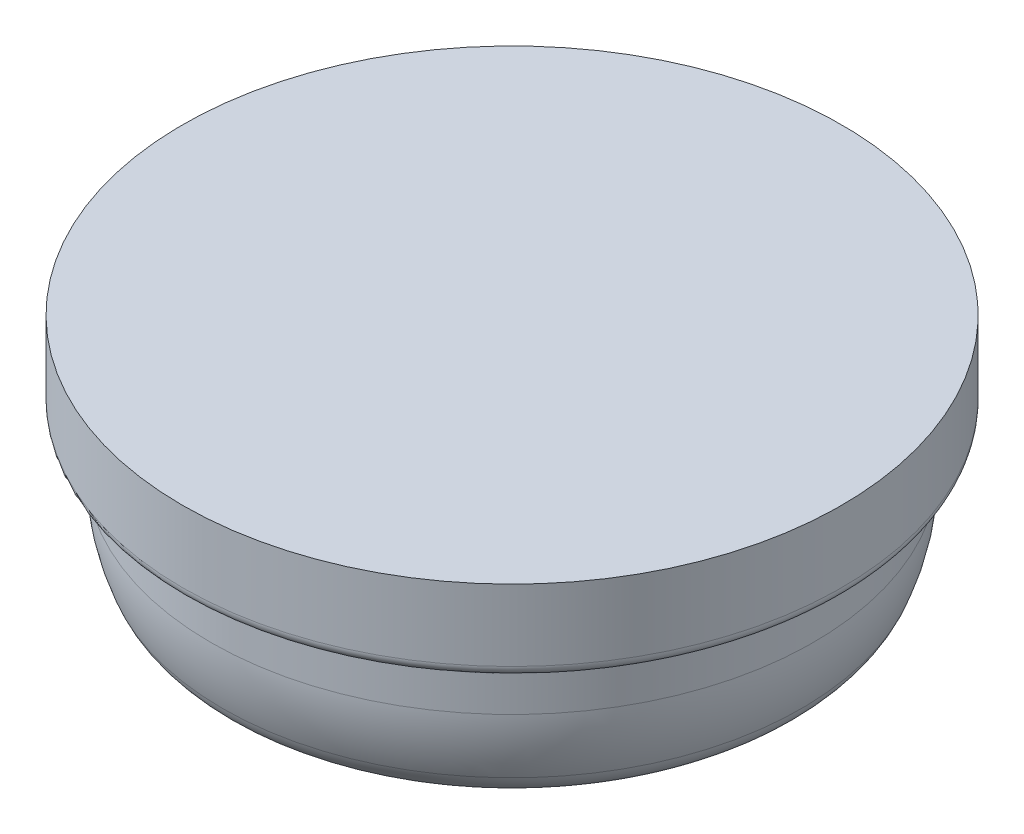
SolidWorks part; units mm, degrees
material "Thornel Mat VMA"
ref_plane "Ground Plane" through (0, 0, 0) normal (0, 0, 1) x (1, 0, 0)
ref_plane "Center Plane" through (0, 0, 0) normal (0, 1, 0) x (1, 0, 0)
ref_plane "Left Plane" through (0, 0, 0) normal (1, 0, 0) x (0, 0, -1)
ref_axis "FRONT (X)" through (88.99, 0, 0) along (-1, 0, 0)
ref_axis "LEFT (Y)" through (0, 55, 0) along (0, -1, 0)
ref_axis "UP (Z)" through (0, 0, 55) along (0, 0, -1)
sketch "Sketch1" plane through (0, 0, 0) normal (1, 0, 0) x (0, 0, -1)
  line L1 (-80.264, 13.0473) -> (0, 13.0473)
  line L4 (0, 55) -> (0, -55) construction
  line L5 (0, 13.0473) -> (0, 0) construction
  line L6 (-91.186, 13.0473) -> (-80.264, 13.0473)
  line L7 (-99.2127, 14.8321) -> (-112.2985, 20.9525)
  line L8 (-138.5553, 113.3653) -> (0, 113.3653)
  line L9 (-112.2985, 5.1421) -> (-112.2985, 20.9525) construction
  line L10 (-112.2985, 13.0473) -> (-91.186, 13.0473) construction
  line L12 (0, 113.3653) -> (0, 0)
  line L21 (-126.6825, 72.5011) -> (-126.6825, 57.5011)
  line L22 (-138.5553, 83.3653) -> (-138.5553, 113.3653)
  arc A2 (-121.6299, 30.884) -> (-112.2985, 20.9525) centre (-104.4975, 37.6315) ccw
  arc A3 (-121.6299, 30.884) -> (-126.6825, 57.5011) centre (-54.0473, 57.5011) cw
  arc A12 (-126.6825, 72.5011) -> (-133.6675, 78.8193) centre (-133.0325, 72.5011) ccw
  arc A13 (-138.5553, 83.3653) -> (-133.6675, 78.8193) centre (-134.112, 83.242) ccw
  arc A14 (-137.2648, 85.2011) -> (-138.5553, 83.3653) centre (-136.5241, 83.3089) ccw construction
  arc A16 (-131.445, 83.8993) -> (-137.2648, 85.2011) centre (-135.3204, 80.2342) ccw construction
  arc A17 (-130.1099, 82.1057) -> (-131.445, 83.8993) centre (-138.3653, 77.3544) ccw construction
  arc A18 (-130.1099, 82.1057) -> (-129.0777, 81.1663) centre (-128.1286, 83.246) ccw construction
  arc A20 (-123.5075, 72.5011) -> (-129.0777, 81.1663) centre (-133.0325, 72.5011) ccw construction
  spline S0 degree 3 poles (-91.186, 13.0473) (-93.9931, 13.0473) (-96.7097, 13.6614) (-99.2127, 14.8321) knots 0 0 0 0 1 1 1 1 weights 0.254333 0.254333 0.2585 0.266833
  dimension "D2" = 30
sketch "Sketch2" [suppressed] plane through (0, 0, 0) normal (0, 1, 0) x (1, 0, 0)
  line L0 (82.804, 22.1873) -> (-82.804, -22.1873) construction
  line L1 (0, 0) -> (-62.4463, 0) construction
  line L2 (88.99, 0) -> (-88.99, 0) construction
  circle A0 centre (-82.804, -22.1873) radius 3.175
  circle A1 centre (-82.804, 22.1873) radius 3.175
  circle A2 centre (-60.6167, 60.6167) radius 3.175
  circle A3 centre (-22.1873, 82.804) radius 3.175
  circle A4 centre (22.1873, 82.804) radius 3.175
  circle A5 centre (60.6167, 60.6167) radius 3.175
  circle A6 centre (82.804, 22.1873) radius 3.175
  circle A7 centre (82.804, -22.1873) radius 3.175
  circle A8 centre (60.6167, -60.6167) radius 3.175
  circle A9 centre (22.1873, -82.804) radius 3.175
  circle A10 centre (-22.1873, -82.804) radius 3.175
  circle A11 centre (-60.6167, -60.6167) radius 3.175
  point P6 (0, 0)
  point P34 (0, 0)
  dimension "D3" = 6.35
  dimension "D1" = 171.45
  dimension "D2" = 15
  dimension "D4" = 12
revolve "Revolve1" add sketch "Sketch1" angle 360 about axis through (0, 55, 0) along (0, -1, 0) region at (0, 65.2663, 64.2497)
sketch "Sketch3" plane through (0, 113.3653, 0) normal (0, 1, 0) x (1, 0, 0)
  line L0 (-138.5553, 0) -> (138.5553, 0) construction
  line L1 (88.99, 0) -> (-88.99, 0) construction
  circle A0 centre (0, 0) radius 138.5553 construction
  point P6 (0, 0)
  point P7 (0, 0)
